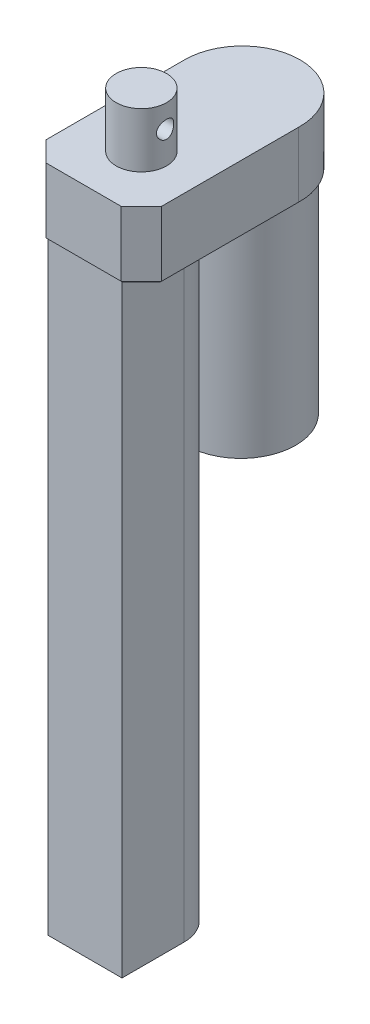
SolidWorks part; units mm, degrees
ref_plane "Alzado" through (0, 0, 0) normal (0, 0, 1) x (1, 0, 0)
ref_plane "Planta" through (0, 0, 0) normal (0, 1, 0) x (1, 0, 0)
ref_plane "Vista lateral" through (0, 0, 0) normal (1, 0, 0) x (0, 0, -1)
sketch "Croquis1" plane through (0, 0, 0) normal (0, 1, 0) x (1, 0, 0)
  line L0 (0, -27.25) -> (0, 47.75) construction
  line L1 (-20, -27.25) -> (20, -27.25)
  line L2 (-20, -27.25) -> (-20, 27.25)
  line L4 (20, -27.25) -> (20, 27.25)
  line L5 (-20, -27.25) -> (20, 27.25) construction
  line L6 (-20, 27.25) -> (20, -27.25) construction
  arc A1 (20, 27.25) -> (-20, 27.25) centre (0, 27.7439) ccw
  point P0 (0, 0)
  dimension "D1" = 40
  dimension "D2" = 54.5
  dimension "D3" = 75
extrude "Saliente-Extruir1" add sketch "Croquis1" along normal blind 23
chamfer "Chaflán1" distance 7 angle 45 2 edges at (20, 11.5, 27.25) (-20, 11.5, 27.25)
sketch "Croquis2" plane through (0, 23, 0) normal (0, 1, 0) x (1, 0, 0)
  line L0 (-13, -27.25) -> (13, -27.25) construction
  circle A0 centre (0, -7.25) radius 8.75
  dimension "D1" = 17.5
  dimension "D2" = 20
extrude "Saliente-Extruir2" add sketch "Croquis2" along normal blind 19
chamfer "Chaflán2" distance 0.5 angle 45 6 edges at (0, 0, -47.75) (-20, 0, -3.5) (-16.5, 0, 23.75) (0, 0, 27.25) (16.5, 0, 23.75) (20, 0, -3.5)
sketch "Croquis4" plane through (0, 0, 0) normal (0, -1, 0) x (1, 0, 0)
  circle A0 centre (0, -27.25) radius 19
  circle A2 centre (0, 7.25) radius 8.75
  circle A3 centre (0, 7.25) radius 8.75 construction
  dimension "D1" = 38
  dimension "D3" = 34.5
  dimension "D2" = 0
extrude "Saliente-Extruir3" add sketch "Croquis4" along normal blind 73
sketch "Croquis3" plane through (0, 0, 0) normal (1, 0, 0) x (0, 0, -1)
  line L0 (-27.25, 0.5) -> (-27.25, 23) construction
  line L1 (1.5, 42) -> (-16, 42) construction
  circle A0 centre (-7.25, 34) radius 3
  dimension "D1" = 6
  dimension "D2" = 20
  dimension "D3" = 8
extrude "Cortar-Extruir1" cut sketch "Croquis3" against normal mid plane 25
sketch "Croquis5" plane through (0, 0, 0) normal (0, -1, 0) x (1, 0, 0)
  line L0 (-12.7929, 26.75) -> (-12.7929, 5.25)
  line L1 (12.7929, 5.25) -> (12.7929, 26.75)
  line L5 (-19.5, 20.0429) -> (-19.5, -27.2562)
  line L6 (19.5, -27.2562) -> (19.5, 20.0429)
  line L7 (19.5, 20.0429) -> (12.7929, 26.75)
  line L8 (12.7929, 26.75) -> (-12.7929, 26.75)
  line L9 (-12.7929, 26.75) -> (-19.5, 20.0429)
  line L10 (-19.5, 20.0429) -> (-19.5, -27.2562)
  line L11 (19.5, -27.2562) -> (19.5, 20.0429)
  line L12 (19.5, 20.0429) -> (12.7929, 26.75)
  line L13 (12.7929, 26.75) -> (-12.7929, 26.75)
  line L14 (-12.7929, 26.75) -> (-19.5, 20.0429)
  arc A0 (-12.7929, 5.25) -> (12.7929, 5.25) centre (0, 5.25) ccw
  arc A1 (-19.5, -27.2562) -> (19.5, -27.2562) centre (0, -27.7439) ccw
  arc A2 (-19.5, -27.2562) -> (19.5, -27.2562) centre (0, -27.7439) ccw
  line M12 (12.7929, 26.75) -> (-12.7929, 26.75)
  dimension "D2" = 21.5
  dimension "D1" = 0
extrude "Saliente-Extruir7" add sketch "Croquis5" along normal blind 209 contours L0 A0 L1 M12 region at (0, 0, 10.847)
sketch "Croquis6" plane through (0, -209, 0) normal (0, -1, 0) x (1, 0, 0)
  circle A0 centre (0, 7.25) radius 10
  circle A1 centre (0, 7.25) radius 8.75
  circle A2 centre (0, 7.25) radius 8.75 construction
  dimension "D1" = 0
extrude "Cortar-Extruir2" cut sketch "Croquis6" against normal blind 150
ref_point "Point1"
